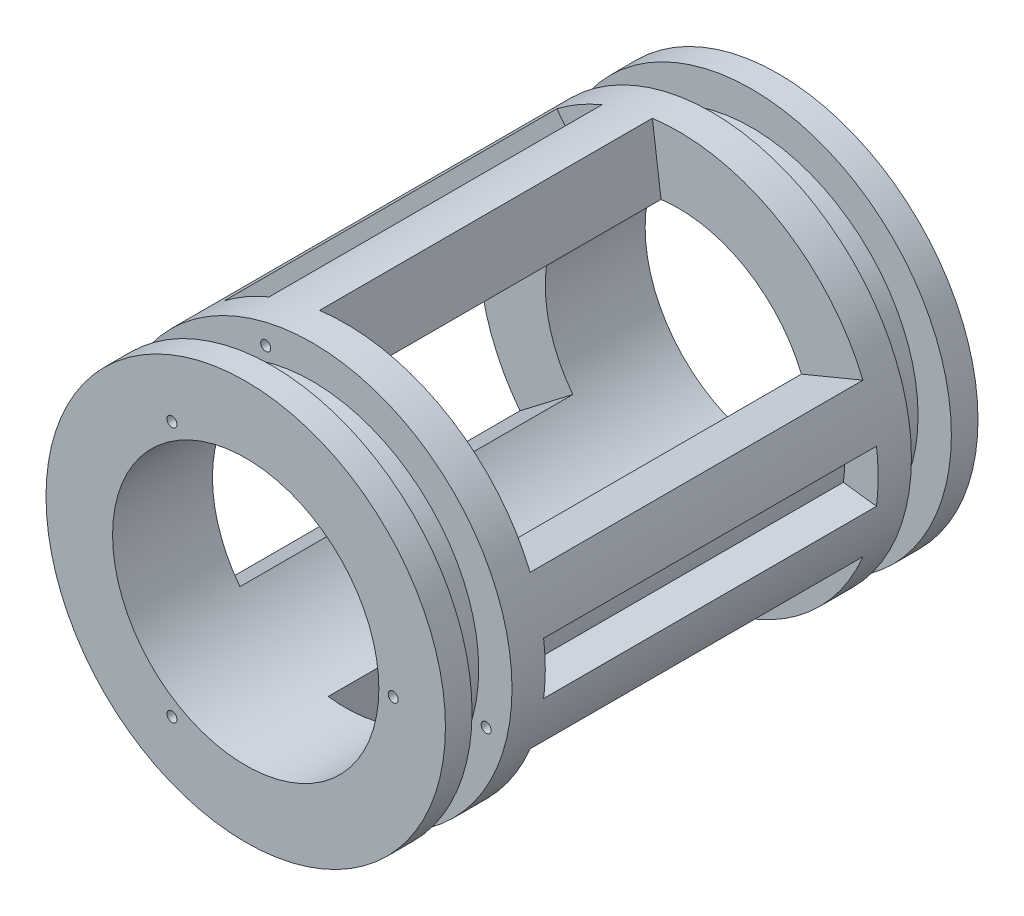
SolidWorks part; units mm, degrees
ref_plane "前视基准面" through (0, 0, 0) normal (0, 0, 1) x (1, 0, 0)
ref_plane "上视基准面" through (0, 0, 0) normal (0, 1, 0) x (1, 0, 0)
ref_plane "右视基准面" through (0, 0, 0) normal (1, 0, 0) x (0, 0, -1)
other "Configuration Table"
sketch "草图1" plane through (0, 0, 0) normal (0, 0, 1) x (1, 0, 0)
  circle A0 centre (0, 0) radius 25
  circle A1 centre (0, 0) radius 20
  dimension "D1" = 50
  dimension "D2" = 40
extrude "凸台-拉伸1" add sketch "草图1" along normal blind 40
sketch "草图2" plane through (0, 0, 40) normal (0, 0, 1) x (1, 0, 0)
  circle A0 centre (0, 0) radius 25 construction
  circle A1 centre (0, 0) radius 25
  circle A2 centre (0, 0) radius 30
  dimension "D1" = 60
extrude "凸台-拉伸2" add sketch "草图2" against normal blind 15
sketch "草图3" plane through (0, 0, 25) normal (0, 0, -1) x (-1, 0, 0)
  line L0 (0, 25) -> (0, -30) construction
  line L1 (0, 0) -> (30, 0) construction
  line L4 (-29.7433, -3.9158) -> (0, 0) construction
  line L5 (0, 0) -> (-27.7164, -11.4805) construction
  line L8 (-29.7433, 3.9158) -> (0, 0) construction
  line L9 (0, 0) -> (-27.7164, 11.4805) construction
  line L10 (-24.7861, 3.2632) -> (-29.7433, 3.9158)
  line L11 (-27.7164, 11.4805) -> (-23.097, 9.5671)
  line L12 (-29.7433, -3.9158) -> (-24.7861, -3.2632)
  line L13 (-27.7164, -11.4805) -> (-23.097, -9.5671)
  arc A0 (-29.7433, 3.9158) -> (-27.7164, 11.4805) centre (0, 0) cw
  arc A1 (-24.7861, 3.2632) -> (-23.097, 9.5671) centre (0, 0) cw
  circle A4 centre (0, 0) radius 30 construction
  circle A6 centre (0, 0) radius 25 construction
  circle A8 centre (0, 0) radius 25 construction
  circle A9 centre (0, 0) radius 25 construction
  arc A10 (-24.7861, -3.2632) -> (-23.097, -9.5671) centre (0, 0) ccw
  circle A11 centre (0, 0) radius 30 construction
  arc A12 (-29.7433, -3.9158) -> (-27.7164, -11.4805) centre (0, 0) ccw
  dimension "D3" = 15
  dimension "D1" = 15
  dimension "D2" = 7.5
  dimension "D4" = 7.5
extrude "凸台-拉伸3" add sketch "草图3" along normal up to surface (25 mm away) up to face at (25, 0, 0)
pattern_circular "阵列(圆周)1" count 3 over 360 about axis through (0, 0, 40) along (0, 0, -1) of "凸台-拉伸3"
sketch "草图5" plane through (0, 0, 0) normal (0, 0, -1) x (-1, 0, 0)
  line L0 (-23.097, 9.5671) -> (-18.4776, 7.6537)
  line L1 (3.2632, 24.7861) -> (2.6105, 19.8289)
  line L2 (-27.7164, 11.4805) -> (-23.097, 9.5671) construction
  line L3 (-27.7164, 11.4805) -> (-23.097, 9.5671) construction
  line L4 (3.2632, 24.7861) -> (3.9158, 29.7433) construction
  line L5 (3.2632, 24.7861) -> (3.9158, 29.7433) construction
  arc A0 (3.2632, 24.7861) -> (-23.097, 9.5671) centre (0, 0) ccw construction
  arc A1 (3.2632, 24.7861) -> (-23.097, 9.5671) centre (0, 0) ccw
  circle A2 centre (0, 0) radius 20 construction
  arc A3 (-18.4776, 7.6537) -> (2.6105, 19.8289) centre (0, 0) cw
extrude "切除-拉伸1" cut sketch "草图5" against normal blind 25
pattern_circular "阵列(圆周)2" count 3 every 120 about axis through (0, 0, 40) along (0, 0, -1) of "切除-拉伸1" reverse direction yes
sketch "草图6" plane through (0, 0, 40) normal (0, 0, 1) x (1, 0, 0)
  line L0 (-12.3374, 21.3691) -> (-9.8209, 17.0103) construction
  circle A0 centre (-11.0792, 19.1897) radius 0.75
  circle A3 centre (22.1584, 0) radius 0.75
  circle A4 centre (-11.0792, -19.1897) radius 0.75
  arc A5 (-9.5671, 23.097) -> (-15.219, 19.8338) centre (0, 0) ccw construction
  point P6 (-12.5, 21.6506)
  point P16 (0, 0)
  dimension "D1" = 1.5
  dimension "D2" = 3
extrude "切除-拉伸2" cut sketch "草图6" against normal blind 40
sketch "草图10" plane through (0, 0, 0) normal (0, 0, -1) x (-1, 0, 0)
  line L0 (-22.1584, 0.75) -> (-24.9887, 0.75)
  line L1 (-22.1584, -0.75) -> (-24.9887, -0.75)
  line L2 (-22.1584, 0.75) -> (-22.1584, -0.75)
  line L3 (-22.1584, 0) -> (-26.1464, 0) construction
  line L4 (-26.1464, 0) -> (-26.1464, 0.75)
  line L5 (-26.1464, 0.75) -> (-24.9887, 0.75)
  line L6 (-26.1464, 0) -> (-26.1464, -0.75)
  line L7 (-26.1464, -0.75) -> (-24.9887, -0.75)
  circle A2 centre (-22.1584, 0) radius 0.75 construction
revolve "切除-旋转3" cut sketch "草图10" angle 360 about L3 region at (23.8656, 0.3895, 0) region at (22.4767, 0.3183, 0) region at (25.5713, 0.3756, 0)
pattern_circular "阵列(圆周)4" count 3 every 120 about axis through (0, 0, 40) along (0, 0, -1) of "切除-旋转3" reverse direction yes
ref_plane "基准面1" through (0, 0, 33) normal (0, 0, 1) x (1, 0, 0)
sketch "草图11" plane through (0, 0, 33) normal (0, 0, 1) x (1, 0, 0)
  circle A0 centre (0, 0) radius 30 construction
  circle A1 centre (0, 0) radius 30
  circle A2 centre (0, 0) radius 25
extrude "切除-拉伸3" cut sketch "草图11" against normal blind 3 and the other way blind 3
sketch "草图12" plane through (0, 0, 40) normal (0, 0, 1) x (1, 0, 0)
  line L0 (0, 0) -> (0, 30) construction
  circle A0 centre (0, 27) radius 0.75
  circle A1 centre (0, 0) radius 30 construction
  dimension "D1" = 1.5
  dimension "D2" = 3
sketch "草图13" plane through (0, 0, 30) normal (0, 0, 1) x (1, 0, 0)
  line L0 (-3.9158, 29.7433) -> (-9.5671, 23.097) construction
  line L1 (-3.2632, 24.7861) -> (-11.4805, 27.7164) construction
  line L2 (-3.9158, 29.7433) -> (-2.6105, 19.8289) construction
  circle A0 centre (-6.9983, 26.1181) radius 0.75
  dimension "D1" = 1.5
extrude "切除-拉伸5" cut sketch "草图13" against normal through all
pattern_circular "阵列(圆周)3" count 3 over 360 about axis through (0, 0, 25) along (0, 0, 1) of "切除-拉伸5" reverse direction yes
mirror "镜向1" about plane through (0, 0, 0) normal (0, 0, 1) of bodies 120 112
